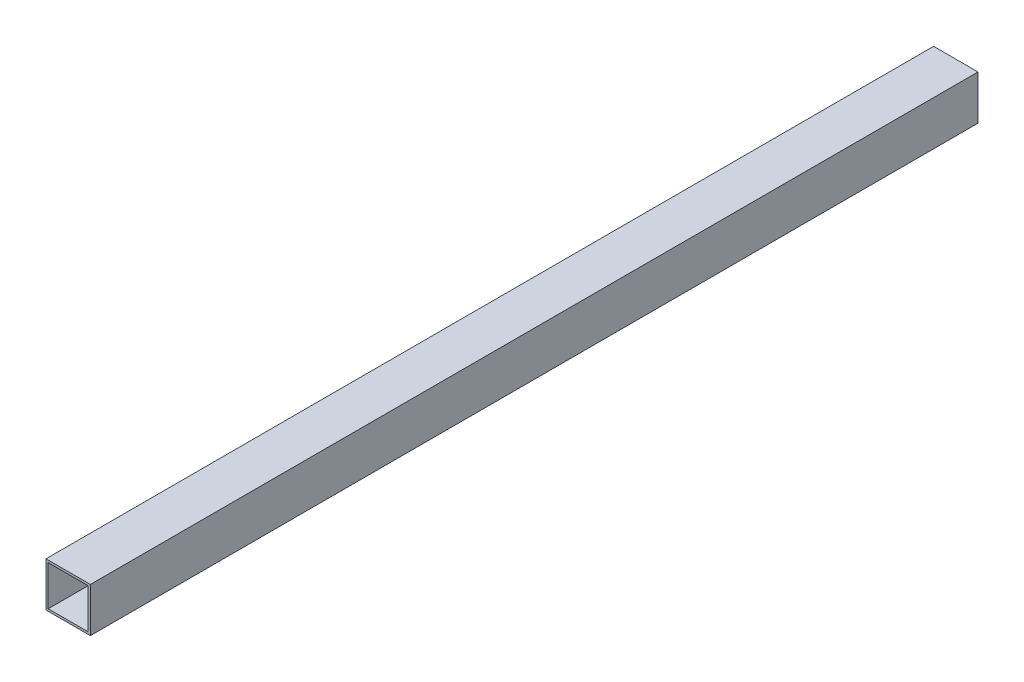
SolidWorks part; units mm, degrees
material "1060 合金"
ref_plane "前视基准面" through (0, 0, 0) normal (0, 0, 1) x (1, 0, 0)
ref_plane "上视基准面" through (0, 0, 0) normal (0, 1, 0) x (1, 0, 0)
ref_plane "右视基准面" through (0, 0, 0) normal (1, 0, 0) x (0, 0, -1)
other "Configuration Table"
sketch "草图1" plane through (0, 0, 0) normal (0, 0, 1) x (1, 0, 0)
  line L1 (0, 0) -> (20, 0)
  line L2 (0, 0) -> (0, -20)
  line L3 (0, -20) -> (20, -20)
  line L4 (20, 0) -> (20, -20)
  dimension "D1" = 20
  dimension "D2" = 20
extrude "拉伸-薄壁1" add sketch "草图1" along normal blind 400 thin thin type one direction reverse wall 1
